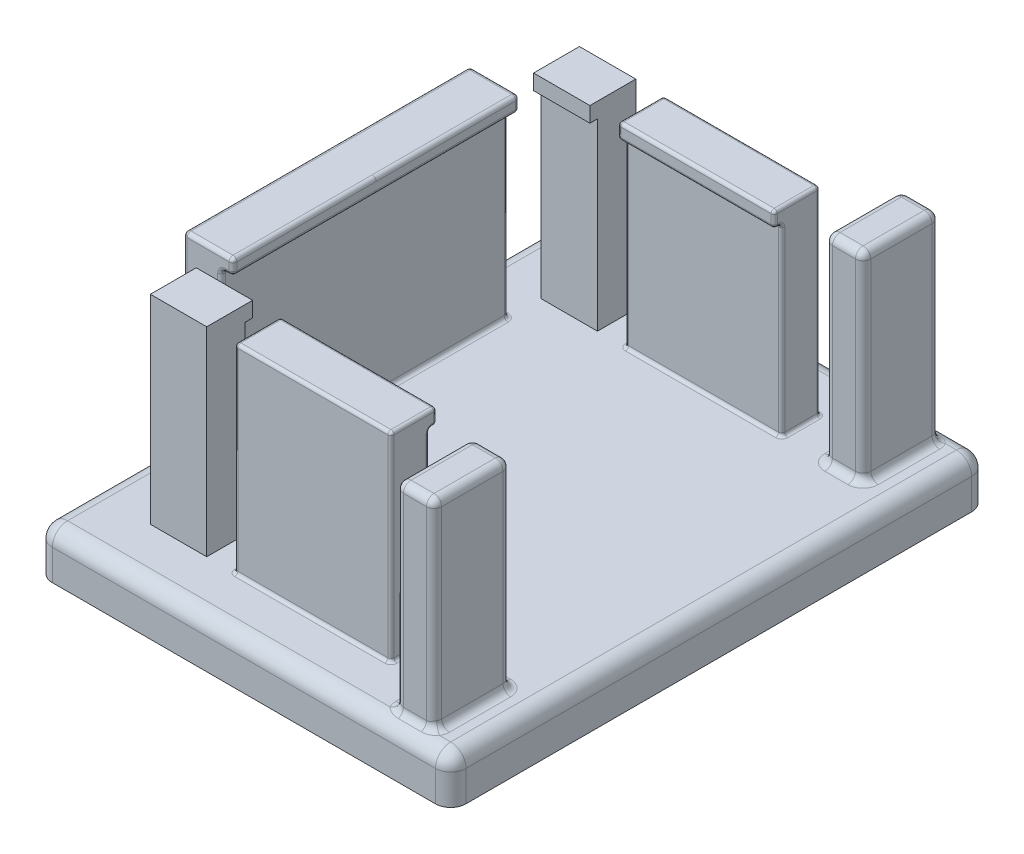
SolidWorks part; units mm, degrees
ref_plane "Front Plane" through (0, 0, 0) normal (0, 0, 1) x (1, 0, 0)
ref_plane "Top Plane" through (0, 0, 0) normal (0, 1, 0) x (1, 0, 0)
ref_plane "Right Plane" through (0, 0, 0) normal (1, 0, 0) x (0, 0, -1)
sketch "Sketch1" plane through (0, 0, 0) normal (0, 1, 0) x (1, 0, 0)
  line L1 (-63.0216, -10.522) -> (-36.0216, -10.522)
  line L2 (-63.0216, -10.522) -> (-63.0216, -45.522)
  line L3 (-63.0216, -45.522) -> (-36.0216, -45.522)
  line L4 (-36.0216, -10.522) -> (-36.0216, -45.522)
  dimension "D1" = 35
extrude "Boss-Extrude1" add sketch "Sketch1" along normal blind 3
fillet "Fillet1" radius 1 1 edges at (-36.0216, 3, 28.022)
fillet "Fillet2" radius 1 7 edges at (-36.0216, 1, 10.522) (-36.3145, 2.7071, 10.522) (-36.0216, 1, 45.522) (-36.3145, 2.7071, 45.522) (-50.0216, 3, 10.522) (-63.0216, 3, 28.022) (-50.0216, 3, 45.522)
fillet "Fillet3" radius 1 2 edges at (-63.0216, 1, 45.522) (-62.7287, 2.7071, 45.2292)
fillet "Fillet4" radius 1 2 edges at (-63.0216, 1, 10.522) (-62.7287, 2.7071, 10.8149)
sketch "Sketch2" plane through (0, 3, 0) normal (0, 1, 0) x (1, 0, 0)
  line L0 (-37.0216, -14.1116) -> (-59.1216, -14.1116) construction
  line L1 (-37.0216, -44.522) -> (-37.0216, -11.522) construction
  line L3 (-37.0216, -11.522) -> (-62.0216, -11.522) construction
  line L4 (-62.0216, -44.522) -> (-37.0216, -44.522) construction
  line L5 (-62.0216, -11.522) -> (-62.0216, -16.872) construction
  line L6 (-62.0216, -44.522) -> (-62.0216, -39.522) construction
  line L7 (-62.0216, -11.522) -> (-62.0216, -44.522) construction
  line L8 (-62.0216, -39.522) -> (-37.0216, -39.522) construction
  line L9 (-62.0216, -16.872) -> (-37.0216, -16.872) construction
  line L10 (-37.0216, -19.0185) -> (-43.6216, -19.0185) construction
  line L11 (-64.6475, -11.522) -> (-64.6475, -44.522) construction
  line L12 (-59.1216, -39.522) -> (-43.4216, -39.522)
  line L13 (-59.1216, -39.522) -> (-59.1216, -42.022)
  line L14 (-59.1216, -42.022) -> (-43.4216, -42.022)
  line L15 (-43.4216, -39.522) -> (-43.4216, -42.022)
  line L16 (-64.6475, -28.022) -> (-37.0216, -28.022) construction
  line L17 (-59.1216, -14.022) -> (-43.4216, -14.022)
  line L18 (-43.4216, -16.522) -> (-43.4216, -14.022)
  line L19 (-59.1216, -16.522) -> (-43.4216, -16.522)
  line L20 (-59.1216, -16.522) -> (-59.1216, -14.022)
  line L21 (-59.1216, -37.372) -> (-61.6216, -37.372)
  line L22 (-59.1216, -28.022) -> (-61.6216, -28.022)
  line L26 (-59.1216, -40.772) -> (-53.7216, -40.772) construction
  line L28 (-53.7216, -42.022) -> (-56.4216, -42.022)
  line L29 (-53.7216, -42.022) -> (-53.7216, -39.522)
  line L30 (-53.7216, -39.522) -> (-56.4216, -39.522)
  line L31 (-56.4216, -42.022) -> (-56.4216, -39.522)
  line L32 (-53.7216, -16.522) -> (-56.4216, -16.522)
  line L33 (-56.4216, -14.022) -> (-56.4216, -16.522)
  line L34 (-53.7216, -14.022) -> (-56.4216, -14.022)
  line L35 (-53.7216, -14.022) -> (-53.7216, -16.522)
  line L36 (-61.6216, -28.022) -> (-61.6216, -37.372)
  line L37 (-43.4216, -42.022) -> (-40.6081, -42.022)
  line L38 (-43.4216, -42.022) -> (-43.4216, -39.522)
  line L39 (-43.4216, -39.522) -> (-40.6081, -39.522)
  line L40 (-40.6081, -42.022) -> (-40.6081, -39.522)
  line L41 (-40.6081, -39.522) -> (-38.1081, -39.522)
  line L42 (-40.6081, -39.522) -> (-40.6081, -44.522)
  line L43 (-40.6081, -44.522) -> (-38.1081, -44.522)
  line L44 (-38.1081, -39.522) -> (-38.1081, -44.522)
  line L45 (-59.1216, -37.372) -> (-59.1216, -28.022)
  point P24 (-62.0216, -14.197)
  dimension "D1" = 33
  dimension "D2" = 15.7
  dimension "D3" = 23
  dimension "D4" = 11.5
  dimension "D5" = 2.5
  dimension "D6" = 2.5
  dimension "D7" = 2.5
extrude "Boss-Extrude5" add sketch "Sketch2" along normal blind 13 contours L14 L15 L12 L13
sketch "Sketch4" plane through (0, 16, 0) normal (0, 1, 0) x (1, 0, 0)
  line L0 (-59.1216, -40.772) -> (-57.1216, -40.772) construction
  line L1 (-59.1216, -39.522) -> (-59.1216, -42.022) construction
  line L2 (-59.1216, -39.522) -> (-43.4216, -39.522) construction
  line L3 (-53.6216, -39.522) -> (-55.4453, -39.522)
  line L4 (-53.6216, -39.522) -> (-53.6216, -42.022)
  line L5 (-53.6216, -42.022) -> (-55.4453, -42.022)
  line L6 (-55.4453, -39.522) -> (-55.4453, -42.022)
  line L7 (-59.1216, -42.022) -> (-43.4216, -42.022) construction
extrude "Cut-Extrude1" cut sketch "Sketch4" against normal blind 13
extrude "Boss-Extrude7" add sketch "Sketch2<7>" along normal blind 13 contours L44 L41 L40 L42 L1 region at (-39.3581, 3, 42.022)
sketch "Sketch2<7>" plane through (0, 3, 0) normal (0, 1, 0) x (1, 0, 0) same geometry as "Sketch2"
extrude "Boss-Extrude8" add sketch "Sketch2<8>" along normal blind 13 contours L21 L22 region at (-60.3716, 3, 32.697)
sketch "Sketch2<8>" plane through (0, 3, 0) normal (0, 1, 0) x (1, 0, 0) same geometry as "Sketch2"
sketch "Sketch8" plane through (0, 0, 39.522) normal (0, 0, -1) x (-1, 0, 0)
  line L0 (43.4216, 16) -> (43.4216, 15)
  line L1 (43.4216, 16) -> (43.4216, 3) construction
  line L2 (43.4216, 15) -> (53.6216, 15)
  line L3 (53.6216, 3) -> (53.6216, 16) construction
  line L4 (53.6216, 15) -> (53.6216, 16)
  line L5 (53.6216, 16) -> (43.4216, 16) construction
  line L6 (53.6216, 16) -> (43.4216, 16)
  line L7 (55.4453, 16) -> (55.4453, 15)
  line L8 (55.4453, 3) -> (55.4453, 16) construction
  line L9 (55.4453, 15) -> (59.1216, 15)
  line L10 (59.1216, 16) -> (59.1216, 3) construction
  line L11 (59.1216, 15) -> (59.1216, 16)
  line L12 (59.1216, 16) -> (55.4453, 16)
sketch "Sketch9" plane through (-59.1216, 0, 0) normal (1, 0, 0) x (0, 0, -1)
  line L0 (-28.022, 16) -> (-28.022, 3) construction
  line L1 (-37.372, 16) -> (-28.022, 16)
  line L2 (-37.372, 16) -> (-37.372, 15)
  line L3 (-37.372, 15) -> (-28.022, 15)
  line L4 (-28.022, 16) -> (-28.022, 15)
extrude "Boss-Extrude13" add sketch "Sketch9" along normal blind 0.742
extrude "Boss-Extrude12" add sketch "Sketch8" along normal blind 0.492 contours L2 L4 L6 L0 | L9 L11 L12 L7
fillet "Fillet64" radius 0.5 12 edges at (-39.3581, 3, 39.522) (-40.6081, 9.5, 39.522) (-40.6081, 3, 42.022) (-40.6081, 9.5, 44.522) (-39.3581, 3, 44.522) (-39.3581, 16, 44.522) (-40.6081, 16, 42.022) (-39.3581, 16, 39.522) (-38.1081, 9.5, 44.522) (-38.1081, 16, 42.022) (-38.1081, 9.5, 39.522) (-38.1081, 3, 42.022)
fillet "Fillet65" radius 0.2032 18 edges at (-48.5216, 15, 39.03) (-48.5216, 3, 39.522) (-48.5216, 15, 39.522) (-43.4216, 9, 39.522) (-43.4216, 3, 40.772) (-53.6216, 3, 40.772) (-53.6216, 9, 39.522) (-43.4216, 9.5, 42.022) (-48.5216, 3, 42.022) (-53.6216, 9.5, 42.022) (-48.5216, 16, 39.03) (-43.4216, 16, 40.526) (-48.5216, 16, 42.022) (-53.6216, 16, 40.526) (-43.4216, 15.5, 39.03) (-43.4216, 15, 39.276) (-53.6216, 15, 39.276) (-53.6216, 15.5, 39.03)
fillet "Fillet67" radius 0.254 12 edges at (-60.3716, 3, 37.372) (-58.7506, 15, 37.372) (-58.3796, 15, 32.697) (-59.1216, 3, 32.697) (-59.1216, 9, 37.372) (-59.1216, 15, 32.697) (-61.6216, 9.5, 37.372) (-61.6216, 3, 32.697) (-61.6216, 16, 32.697) (-58.3796, 16, 32.697) (-60.0006, 16, 37.372) (-58.3796, 15.5, 37.372)
ref_plane "Plane6" through (0, 0, 28.022) normal (0, 0, -1) x (-1, 0, 0)
mirror "Mirror13" about plane through (0, 0, 28.022) normal (0, 0, -1) of "Fillet67", "Fillet65", "Fillet64", "Boss-Extrude12", "Boss-Extrude13", "Boss-Extrude8", "Boss-Extrude7", "Cut-Extrude1", "Boss-Extrude5"
